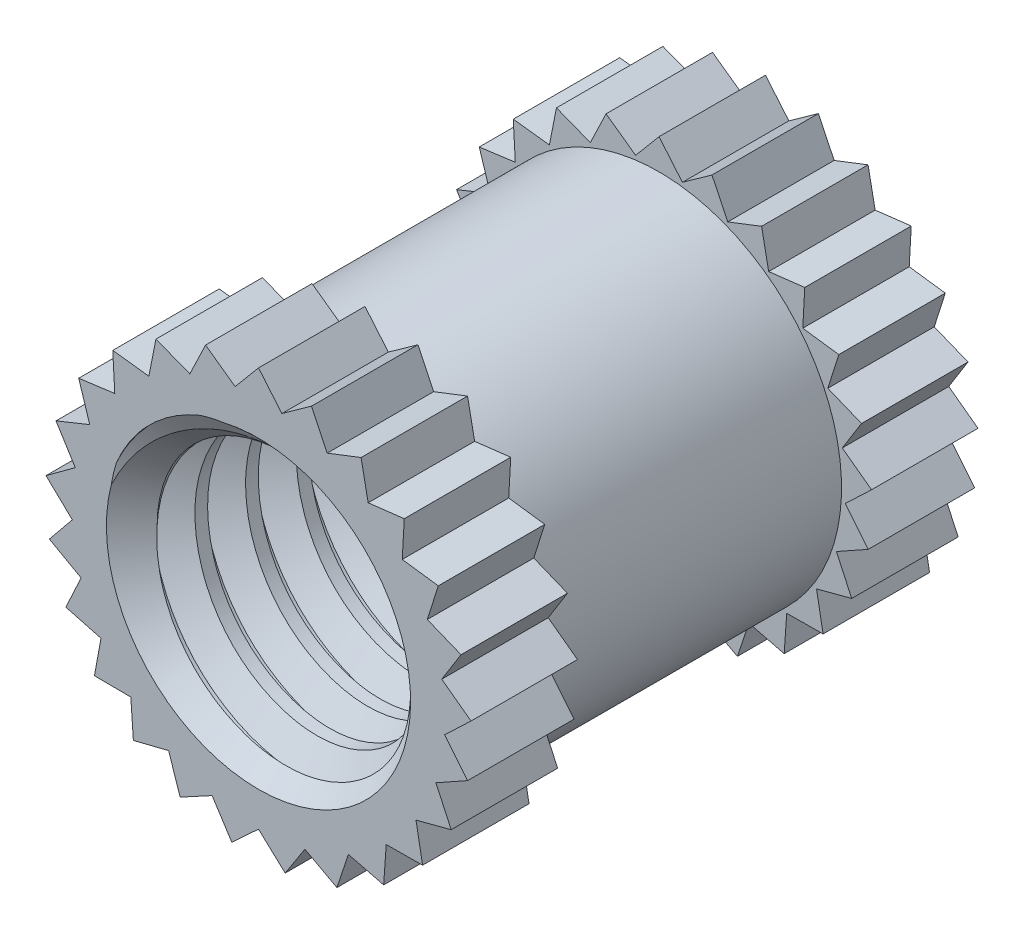
SolidWorks part; units mm, degrees
material "Brass"
ref_plane "Front Plane" through (0, 0, 0) normal (0, 0, 1) x (1, 0, 0)
ref_plane "Top Plane" through (0, 0, 0) normal (0, 1, 0) x (1, 0, 0)
ref_plane "Right Plane" through (0, 0, 0) normal (1, 0, 0) x (0, 0, -1)
sketch "Sketch1" plane through (0, 0, 0) normal (0, 0, 1) x (1, 0, 0)
  circle A1 centre (0, 0) radius 1.8
  dimension "D1" = 3.6
extrude "Boss-Extrude1" add sketch "Sketch1" along normal mid plane 5
hole_wizard "Tap Drill for M3x0.5 Tap1" positions "Sketch2" profile "Sketch3" hole size "M3x0.5" standard "ANSI Metric" end condition through all
sketch "Sketch2" plane through (0, 0, 2.5) normal (0, 0, 1) x (1, 0, 0)
  point P0 (0, 0)
sketch "Sketch3" plane through (0, 0, 2.5) normal (1, 0, 0) x (0, -1, 0)
  line L0 (0, 0) -> (0, 5)
  line L1 (0, 5) -> (1.5, 5)
  line L2 (1.25, 4.75) -> (1.25, 0.25)
  line L3 (1.25, 0.25) -> (1.5, 0)
  line L5 (1.5, 0) -> (0, 0)
  line L6 (-1.25, 0.25) -> (-1.5, 0) construction
  line L7 (1.5, 5) -> (1.25, 4.75)
  line L8 (-1.5, 5) -> (-1.25, 4.75) construction
  line L11 (0, -6.35) -> (0, 107.95) construction
  dimension "Thru Hole Dia." = 2.5
  dimension "Thru Hole Depth" = 5
  dimension "Near C'Sink Dia." = 3
  dimension "Near C'Sink Angle" = 90
  dimension "Far C'Sink Dia." = 3
  dimension "Far C'Sink Angle" = 90
thread "Thread1" pitch 0.5 method cut profile "Thread Profile1" start angle 0, offset 1, length 8, pitch 0.5, diameter 2.5
ref_plane "Plane1" through (-1.25, 0, 3.25) normal (0, -1, 0) x (-1, 0, 0)
sketch "Thread Profile1" plane through (-1.25, 0, 3.25) normal (0, -1, 0) x (-1, 0, 0)
  line L0 (0, 0) -> (0, 0.5) construction
  line L1 (0, 0) -> (0.2706, 0.1562)
  line L2 (0.2706, 0.1562) -> (0.2706, 0.2187)
  line L3 (0.2706, 0.2187) -> (0, 0.375)
  line L4 (0.2706, 0.1875) -> (0, 0.1875) construction
  line L11 (0, 0) -> (0, 0.375)
  point P2 (0, 0)
  dimension "Pitch" = 0.5
  dimension "Profile_Angle" = 60
  dimension "Profile_Land" = 0.0625
  dimension "Profile_Height" = 0.2706
sketch "Sketch6" plane through (0, 0, 2.5) normal (0, 0, 1) x (1, 0, 0)
  line L0 (0, 2.1) -> (0, 0) construction
  line L1 (0, 2.1) -> (-0.2686, 1.7798)
  line L2 (0, 2.1) -> (0.2686, 1.7798)
  circle A0 centre (0, 0) radius 2.1 construction
  circle A1 centre (0, 0) radius 1.8 construction
  arc A2 (0.2686, 1.7798) -> (-0.2686, 1.7798) centre (0, 0) ccw
  dimension "D1" = 4.2
  dimension "D2" = 80
extrude "Boss-Extrude2" add sketch "Sketch6" against normal blind 1.05
pattern_circular "CirPattern1" count 25 over 360 about axis through (0, 0, 2.5) along (0, 0, -1) of "Boss-Extrude2"
mirror "Mirror1" about plane through (0, 0, 0) normal (0, 0, 1) of "CirPattern1"
